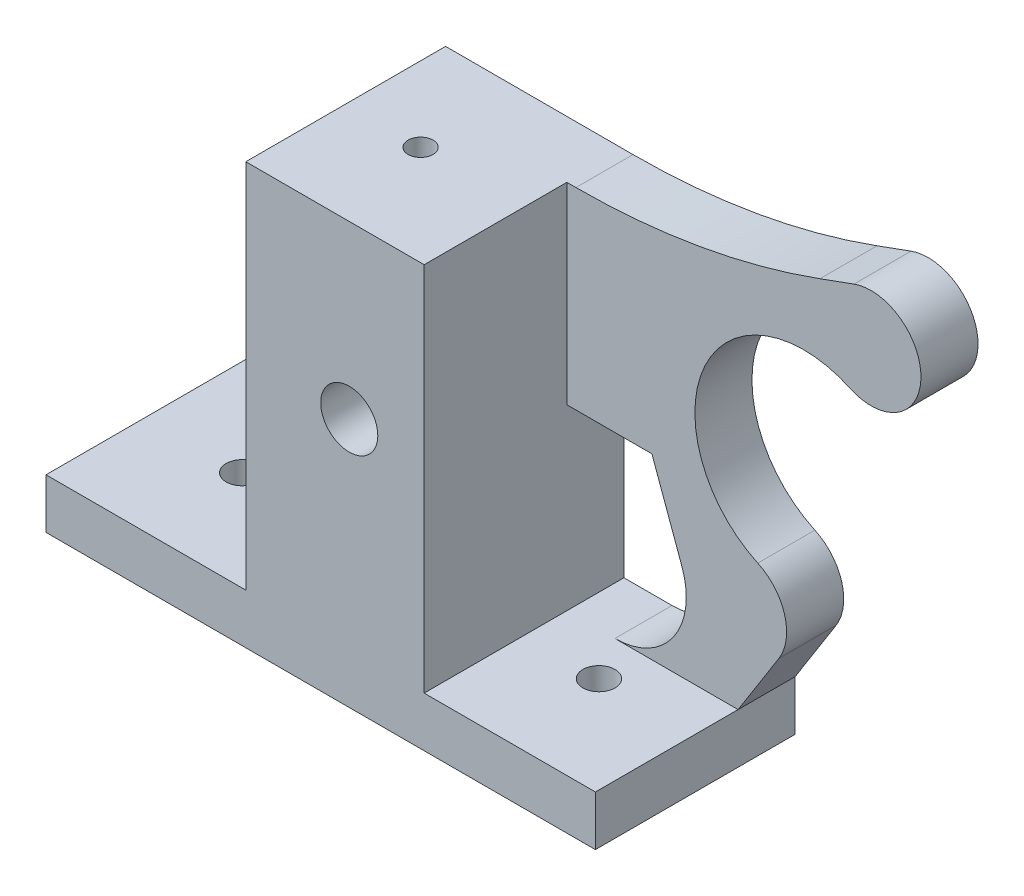
SolidWorks part; units mm, degrees
ref_plane "Front Plane" through (0, 0, 0) normal (0, 0, 1) x (1, 0, 0)
ref_plane "Top Plane" through (0, 0, 0) normal (0, 1, 0) x (1, 0, 0)
ref_plane "Right Plane" through (0, 0, 0) normal (1, 0, 0) x (0, 0, -1)
sketch "Sketch2" plane through (0, 0, 0) normal (0, 0, 1) x (1, 0, 0)
  line L0 (-39.5025, 0) -> (37.4975, 0) construction
  dimension "D1" = 77
sketch "Sketch4" plane through (0, 0, 0) normal (1, 0, 0) x (0, 0, -1)
  line L0 (0, 0) -> (0, 65) construction
  line L1 (0, 0) -> (-28, 0) construction
sketch "Sketch5" plane through (0, 0, 0) normal (0, 0, 1) x (1, 0, 0)
  line L0 (37.4975, 0) -> (-39.5025, 0)
  line L1 (-39.5025, 0) -> (-39.5025, 7)
  line L2 (-39.5025, 7) -> (-11.5, 7)
  line L3 (37.4975, 7) -> (37.4975, 0)
  line L4 (13.5, 7) -> (13.5, 32)
  line L5 (13.5, 32) -> (25.4167, 32)
  line L6 (25.4167, 32) -> (34.516, 7)
  line L7 (56.1283, 60.187) -> (37.3016, 19.813) construction
  line L8 (-11.5, 7) -> (-11.5, 59)
  line L9 (-11.5, 59) -> (32.4005, 59)
  line L10 (32.4005, 59) -> (53.7342, 66.7648)
  line L11 (3, 0) -> (3, 59) construction
  line L12 (26.528, 49.4133) -> (37.3016, 19.813) construction
  line L13 (26.528, 49.4133) -> (56.1283, 60.187) construction
  line L14 (37.3016, 19.813) -> (66.902, 30.5867) construction
  line L15 (56.1283, 60.187) -> (66.902, 30.5867) construction
  line L16 (37.4975, 7) -> (43.2227, 16.0793)
  line L17 (13.5, 7) -> (34.516, 7)
  circle A0 centre (3, 35) radius 11 construction
  circle A1 centre (3, 35) radius 4
  circle A2 centre (3, 35) radius 33 construction
  circle A3 centre (46.715, 40) radius 11 construction
  circle A4 centre (37.3016, 19.813) radius 1.75 construction
  circle A5 centre (26.528, 49.4133) radius 1.75 construction
  circle A6 centre (56.1283, 60.187) radius 1.75 construction
  circle A7 centre (66.902, 30.5867) radius 1.75 construction
  arc A8 (53.17, 53.8428) -> (53.7342, 66.7648) centre (56.1283, 60.187) ccw
  arc A9 (44.3016, 19.813) -> (40.26, 26.1572) centre (37.3016, 19.813) ccw
  arc A10 (44.3016, 19.813) -> (43.2227, 16.0793) centre (37.3016, 19.813) cw
  arc A11 (53.17, 53.8428) -> (40.26, 26.1572) centre (46.715, 40) ccw
  dimension "D1" = 22
  dimension "D7" = 8
  dimension "D10" = 22
  dimension "D11" = 66
  dimension "D14" = 3.5
  dimension "D15" = 7
  dimension "D5" = 33
  dimension "D2" = 7
  dimension "D3" = 25
  dimension "D4" = 25
  dimension "D6" = 31.5
  dimension "D8" = 52
  dimension "D9" = 14.5
  dimension "D12" = 28
  dimension "D13" = 70
  dimension "D16" = 3
extrude "Boss-Extrude1" add sketch "Sketch5" along normal blind 8 contours A11 A8 L10 L9 L8 L2 L1 L0 L3 L17 L4 L5 L6 A9 A1 region at (12.8173, 31.3089, 0)
sketch "Sketch6" plane through (0, 0, 8) normal (0, 0, 1) x (1, 0, 0)
  line L0 (37.4975, 0) -> (-39.5025, 0) construction
  line L1 (-39.5025, 0) -> (-39.5025, 7) construction
  line L2 (-39.5025, 7) -> (-11.5, 7) construction
  line L3 (-11.5, 7) -> (-11.5, 59) construction
  line L4 (37.4975, 0) -> (-39.5025, 0)
  line L5 (-39.5025, 0) -> (-39.5025, 7)
  line L6 (-39.5025, 7) -> (-11.5, 7)
  line L7 (-11.5, 7) -> (-11.5, 59)
  line L8 (37.4975, 0) -> (37.4975, 7)
  line L9 (37.4975, 7) -> (13.5, 7)
  line L10 (13.5, 7) -> (13.5, 59)
  line L11 (-11.5, 59) -> (32.4005, 59) construction
  line L12 (13.5, 59) -> (-11.5, 59)
  line L13 (37.4975, 7) -> (37.4975, 0) construction
  circle A0 centre (3, 35) radius 4 construction
  circle A1 centre (3, 35) radius 4
extrude "Boss-Extrude2" add sketch "Sketch6" along normal blind 20
sketch "Sketch7" plane through (0, 0, 0) normal (0, -1, 0) x (1, 0, 0)
  line L0 (37.4975, 28) -> (-39.5025, 0) construction
  line L1 (-39.5025, 28) -> (37.4975, 0) construction
  circle A0 centre (-1.0025, 14) radius 7.875
  dimension "D1" = 15.75
extrude "Cut-Extrude1" cut sketch "Sketch7" against normal blind 4
ref_axis "Axis1" through (-1.0025, 4, 14) along (0, -1, 0)
sketch "Sketch8" plane through (0, 59, 0) normal (0, 1, 0) x (1, 0, 0)
  circle A0 centre (-1.0025, -14) radius 1.75
  dimension "D1" = 3.5
extrude "Cut-Extrude2" cut sketch "Sketch8" against normal blind 64
sketch "Sketch9" plane through (0, 0, 0) normal (0, -1, 0) x (1, 0, 0)
  line L0 (37.4975, 14) -> (-39.5025, 14) construction
  line L1 (37.4975, 28) -> (37.4975, 0) construction
  line L2 (-39.5025, 28) -> (-39.5025, 0) construction
  circle A0 centre (23.9975, 14) radius 2.25
  circle A1 centre (-26.0025, 14) radius 2.25
  dimension "D1" = 4.5
  dimension "D2" = 50
  dimension "D3" = 13.5
extrude "Cut-Extrude3" cut sketch "Sketch9" against normal blind 64
fillet "Fillet1" radius 10 1 edges
fillet "Fillet2" radius 100 1 edges at (32.4005, 59, 4)
equation "\"D3@Sketch9\"=(77-50)/2"
